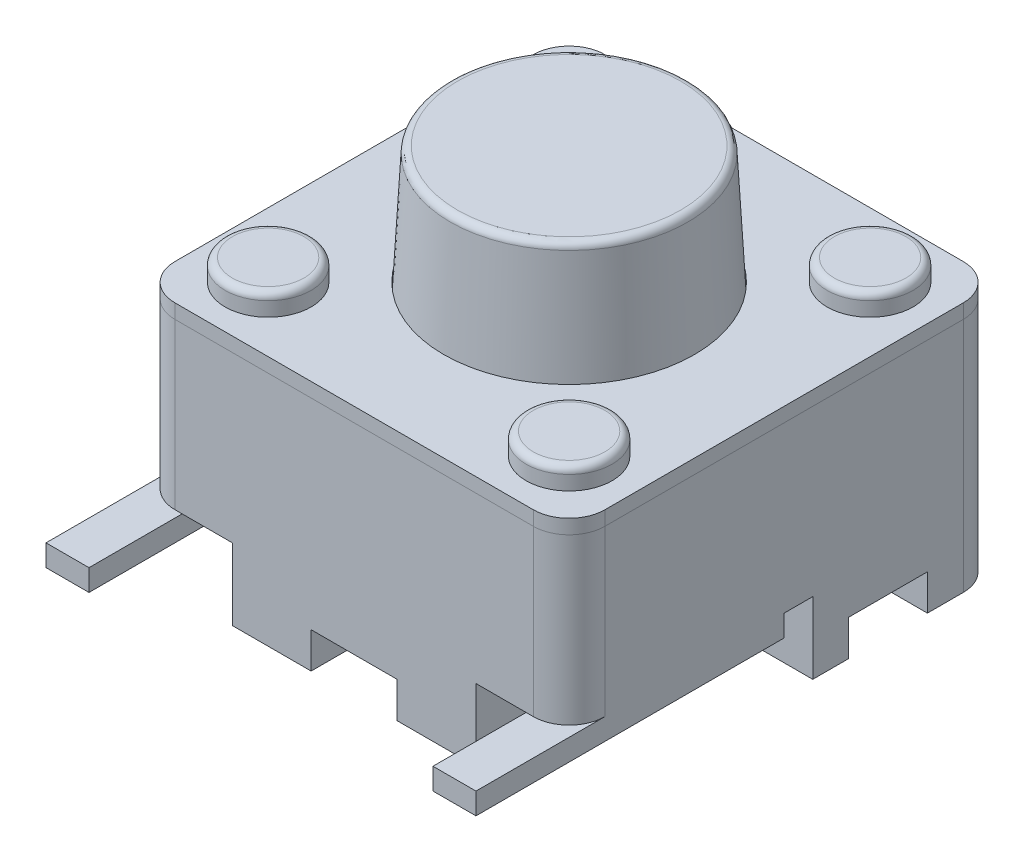
SolidWorks part; units mm, degrees
material "Custom Plastic"
ref_plane "Front Plane" through (0, 0, 0) normal (0, 0, 1) x (1, 0, 0)
ref_plane "Top Plane" through (0, 0, 0) normal (0, 1, 0) x (1, 0, 0)
ref_plane "Right Plane" through (0, 0, 0) normal (1, 0, 0) x (0, 0, -1)
sketch "Sketch1" plane through (0, 0, 0) normal (0, 1, 0) x (1, 0, 0)
  line L0 (-3.2652, 0) -> (3.207, 0) construction
  line L1 (-2.5, 3) -> (2.5, 3)
  line L2 (-3, 2.5) -> (-3, -2.5)
  line L3 (-2.5, -3) -> (2.5, -3)
  line L4 (3, 2.5) -> (3, -2.5)
  line L5 (-3, 3) -> (3, -3) construction
  line L6 (-3, -3) -> (3, 3) construction
  line L7 (0, -3.1905) -> (0, 3.2124) construction
  line L8 (3, 0) -> (2.4, 0)
  line L9 (3, 0) -> (3, -0.3)
  line L10 (3, -0.3) -> (2.4, -0.3)
  line L11 (2.4, 0) -> (2.4, -0.3)
  line L12 (-3, -0.3) -> (-2.4, -0.3)
  line L13 (-2.4, 0) -> (-2.4, -0.3)
  line L14 (-3, 0) -> (-2.4, 0)
  circle A0 centre (2.1, 2.1) radius 0.6
  circle A1 centre (2.1, -2.1) radius 0.6
  circle A2 centre (-2.1, -2.1) radius 0.6
  circle A3 centre (-2.1, 2.1) radius 0.6
  circle A4 centre (0, 0) radius 1.75
  arc A5 (2.5, 3) -> (3, 2.5) centre (2.5, 2.5) cw
  arc A6 (2.5, -3) -> (3, -2.5) centre (2.5, -2.5) ccw
  arc A7 (-3, -2.5) -> (-2.5, -3) centre (-2.5, -2.5) ccw
  arc A8 (-2.5, 3) -> (-3, 2.5) centre (-2.5, 2.5) ccw
  point P0 (0, 0)
  point P1 (0, 0)
  point P9 (0, 0)
  point P18 (0, 0)
  dimension "D1" = 6
  dimension "D2" = 0.9
  dimension "D3" = 1.2
  dimension "D5" = 3.5
  dimension "D6" = 0.5
  dimension "D7" = 0.6
  dimension "D8" = 0.3
  dimension "D4" = 4
extrude "Base" add sketch "Sketch1" along normal blind 3.3 contours L14 L2 L12 L13 | L1 A8 L2 L14 L13 L12 A7 L3 A6 L4 L10 L11 L8 A5 A0 A1 A2 A3 A4 | A3 | A2 | A4 | A1 | L8 L11 L10 L4 | A0 region at (0, 0, -2.9151) region at (-2.7, 0, 0.15) region at (2.7, 0, 0.15) region at (2.1, 0, -2.1) region at (2.1, 0, 2.1) region at (-2.1, 0, 2.1) region at (-2.1, 0, -2.1) region at (0, 0, 0)
extrude "Top Plate" add sketch "Sketch1<3>" along normal blind 0.2 from surface separate body contours L1 A8 L2 L14 L13 L12 A7 L3 A6 L4 L10 L11 L8 A5 A0 A1 A2 A3 A4 | L8 L11 L10 L4 | L14 L2 L12 L13 region at (0, 0, -2.9151) region at (-2.7, 0, 0.15) region at (2.7, 0, 0.15) starting at face at (0, 3.3, 0)
sketch "Sketch1<3>" plane through (0, 0, 0) normal (0, 1, 0) x (1, 0, 0) same geometry as "Sketch1"
extrude "Knobs" add sketch "Sketch1<4>" along normal blind 0.5 from offset 3.3 contours A1 | A2 | A3 | A0 region at (2.1, 0, -2.1) region at (2.1, 0, 2.1) region at (-2.1, 0, 2.1) region at (-2.1, 0, -2.1)
sketch "Sketch1<4>" plane through (0, 0, 0) normal (0, 1, 0) x (1, 0, 0) same geometry as "Sketch1"
extrude "Actuator" add sketch "Sketch1<5>" along normal blind 1.85 draft 3 from surface separate body contours A4 region at (0, 0, 0) starting at face at (-2.1, 3.3, -1.5)
sketch "Sketch1<5>" plane through (0, 0, 0) normal (0, 1, 0) x (1, 0, 0) same geometry as "Sketch1"
sketch "Sketch2" plane through (0, 0, 0) normal (0, -1, 0) x (1, 0, 0)
  line L0 (0, 3) -> (0.6, 3)
  line L1 (0, 3) -> (0, -3) construction
  line L2 (-2.5, 3) -> (2.5, 3) construction
  line L3 (0.6, 3) -> (1.7, 3)
  line L4 (0, -3) -> (0.6, -3)
  line L5 (-1.7, -2) -> (-3, -2)
  line L6 (0.6, -3) -> (0.6, 3)
  line L7 (-1.7, -0.9) -> (-1.7, -2)
  line L8 (-1.7, -0.9) -> (-3, -0.9)
  line L9 (1.7, -0.9) -> (3, -0.9)
  line L10 (1.7, -0.9) -> (1.7, -2)
  line L11 (-3, -0.4) -> (-1.7, -0.4)
  line L12 (-0.6, -3) -> (-0.6, 3)
  line L13 (1.7, 3) -> (1.7, -0.4)
  line L14 (-1.7, 3) -> (-1.7, -0.4)
  line L15 (3, 0) -> (-3, 0) construction
  line L16 (-3, -2.5) -> (-3, 2.5) construction
  line L21 (-2.5, -3) -> (2.5, -3) construction
  line L22 (1.7, -2) -> (3, -2)
  line L23 (3, -2.5) -> (3, 2.5) construction
  line L25 (3, -0.4) -> (1.7, -0.4)
  point P5 (0, 0)
  point P12 (0, 0)
  arc M1 (3, 2.5) -> (2.5, 3) centre (2.5, 2.5) ccw
  line M2 (2.5, 3) -> (-2.5, 3)
  arc M3 (-2.5, 3) -> (-3, 2.5) centre (-2.5, 2.5) ccw
  line M4 (-3, 2.5) -> (-3, -2.5)
  line M6 (-2.5, -3) -> (2.5, -3)
  line M8 (3, -2.5) -> (3, 2.5)
  dimension "D1" = 0.6
  dimension "D2" = 1.7
  dimension "D3" = 0.4
  dimension "D4" = 1
  dimension "D6" = 0.5
extrude "Base Leg Cutout" cut sketch "Sketch2" against normal blind 1 from surface contours L14 L11 M2 M3 M4 | L25 L13 M8 M1 M2 region at (2.3434, 0, 1.2805) region at (-2.3434, 0, 1.2805) starting at face at (0, 0, 0)
extrude "Base Shallow Cutout" cut sketch "Sketch2<3>" against normal blind 0.5 contours L1 L12 M2 M6 | L10 L22 L9 M8 | L7 L8 L5 M4 region at (2.35, 0, -1.45) region at (-2.35, 0, -1.45) region at (0, 0, 0)
sketch "Sketch2<3>" plane through (0, 0, 0) normal (0, -1, 0) x (1, 0, 0) same geometry as "Sketch2"
extrude "Pins" add sketch "Sketch1<7>" against normal blind 0.3 from offset 1 separate body contours L14 L2 L12 L13 | L8 L11 L10 L4 region at (-2.7, 0, 0.15) region at (2.7, 0, 0.15)
sketch "Sketch1<7>" plane through (0, 0, 0) normal (0, 1, 0) x (1, 0, 0) same geometry as "Sketch1"
fillet "Fillet1" radius 0.1 1 edges at (0, 5.15, 1.653)
fillet "Fillet2" radius 0.1 4 edges at (-2.1, 3.8, -1.5) (2.1, 3.8, -1.5) (-2.1, 3.8, 2.7) (2.1, 3.8, 2.7)
sketch "Sketch4" plane through (0, 0, 0.3) normal (0, 0, 1) x (1, 0, 0)
  line L4 (3, 1) -> (2.4, 1)
  line L5 (2.4, 1) -> (2.4, 0.7)
  line L6 (2.4, 0.7) -> (3, 0.7)
  line L7 (3, 0.7) -> (3, 1)
  line L8 (3, 1) -> (2.4, 1)
  line L9 (2.4, 1) -> (2.4, 0.7)
  line L10 (2.4, 0.7) -> (3, 0.7)
  line L11 (3, 0.7) -> (3, 1)
  line L12 (-2.4, 1) -> (-3, 1)
  line L13 (-3, 1) -> (-3, 0.7)
  line L14 (-3, 0.7) -> (-2.4, 0.7)
  line L15 (-2.4, 0.7) -> (-2.4, 1)
  line L16 (-2.4, 1) -> (-3, 1)
  line L17 (-3, 1) -> (-3, 0.7)
  line L18 (-3, 0.7) -> (-2.4, 0.7)
  line L19 (-2.4, 0.7) -> (-2.4, 1)
  dimension "D1" = 0
  dimension "D2" = 0
extrude "Boss-Extrude1" add sketch "Sketch4" along normal blind 4
